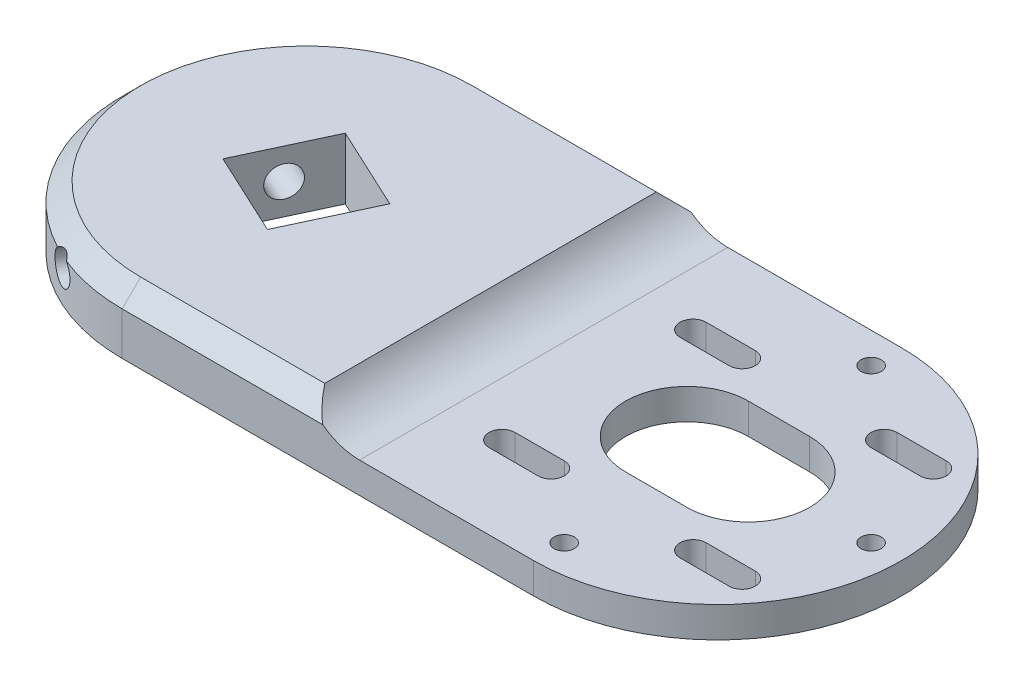
SolidWorks part; units mm, degrees
material "6063-O"
ref_plane "Front Plane" through (0, 0, 0) normal (0, 0, 1) x (1, 0, 0)
ref_plane "Top Plane" through (0, 0, 0) normal (0, 1, 0) x (1, 0, 0)
ref_plane "Right Plane" through (0, 0, 0) normal (1, 0, 0) x (0, 0, -1)
sketch "Sketch1" plane through (0, 0, 0) normal (0, 1, 0) x (1, 0, 0)
  line L0 (-33.5, 0) -> (33.5, 0) construction
  line L1 (-33.5, 30) -> (33.5, 30)
  line L2 (-33.5, -30) -> (33.5, -30)
  line L3 (28.5, 0) -> (38.5, 0) construction
  line L4 (28.5, 10) -> (38.5, 10)
  line L5 (28.5, -10) -> (38.5, -10)
  arc A0 (-33.5, 30) -> (-33.5, -30) centre (-33.5, 0) ccw
  arc A1 (33.5, -30) -> (33.5, 30) centre (33.5, 0) ccw
  arc A2 (28.5, 10) -> (28.5, -10) centre (28.5, 0) ccw
  circle A3 centre (33.5, 0) radius 13.5 construction
  arc A4 (38.5, -10) -> (38.5, 10) centre (38.5, 0) ccw
  point P10 (33.5, 0)
  dimension "D2" = 60
  dimension "D3" = 60
  dimension "D4" = 10
  dimension "D5" = 27
  dimension "D6" = 10
  dimension "D1" = 67
extrude "Boss-Extrude1" add sketch "Sketch1" along normal blind 5
sketch "Sketch2" plane through (0, 5, 0) normal (0, 1, 0) x (1, 0, 0)
  line L0 (13.9437, 15.5563) -> (21.9437, 15.5563) construction
  line L1 (13.9437, 17.6863) -> (21.9437, 17.6863)
  line L2 (13.9437, 13.4263) -> (21.9437, 13.4263)
  line L3 (33.5, 0) -> (33.5, 22) construction
  line L4 (17.9437, 15.5563) -> (33.5, 0) construction
  line L5 (11.5, 0) -> (55.5, 0) construction
  line L6 (53.0563, 15.5563) -> (45.0563, 15.5563) construction
  line L7 (53.0563, 17.6863) -> (45.0563, 17.6863)
  line L8 (53.0563, 13.4263) -> (45.0563, 13.4263)
  line L9 (53.0563, -15.5563) -> (45.0563, -15.5563) construction
  line L10 (53.0563, -17.6863) -> (45.0563, -17.6863)
  line L11 (53.0563, -13.4263) -> (45.0563, -13.4263)
  line L12 (13.9437, -15.5563) -> (21.9437, -15.5563) construction
  line L13 (13.9437, -17.6863) -> (21.9437, -17.6863)
  line L14 (13.9437, -13.4263) -> (21.9437, -13.4263)
  circle A0 centre (33.5, 0) radius 22 construction
  arc A1 (13.9437, 17.6863) -> (13.9437, 13.4263) centre (13.9437, 15.5563) ccw
  arc A2 (21.9437, 13.4263) -> (21.9437, 17.6863) centre (21.9437, 15.5563) ccw
  arc A3 (53.0563, 17.6863) -> (53.0563, 13.4263) centre (53.0563, 15.5563) cw
  arc A4 (45.0563, 13.4263) -> (45.0563, 17.6863) centre (45.0563, 15.5563) cw
  arc A5 (53.0563, -17.6863) -> (53.0563, -13.4263) centre (53.0563, -15.5563) ccw
  arc A6 (45.0563, -13.4263) -> (45.0563, -17.6863) centre (45.0563, -15.5563) ccw
  arc A7 (13.9437, -17.6863) -> (13.9437, -13.4263) centre (13.9437, -15.5563) cw
  arc A8 (21.9437, -13.4263) -> (21.9437, -17.6863) centre (21.9437, -15.5563) cw
  arc A9 (33.5, -30) -> (33.5, 30) centre (33.5, 0) ccw construction
  point P5 (17.9437, 15.5563)
  point P16 (49.0563, 15.5563)
  point P23 (49.0563, -15.5563)
  point P30 (17.9437, -15.5563)
  dimension "D1" = 44
  dimension "D3" = 2.13
  dimension "D2" = 8
  dimension "D4" = 45
extrude "Cut-Extrude1" cut sketch "Sketch2" against normal through all
sketch "Sketch8" plane through (0, 5, 0) normal (0, 1, 0) x (1, 0, 0)
  line L0 (-3.5, 30) -> (-3.5, -30)
  line L1 (33.5, 30) -> (-33.5, 30) construction
  line L2 (-33.5, -30) -> (33.5, -30) construction
  line L3 (-3.5, 30) -> (-33.5, 30)
  line L4 (-3.5, -30) -> (-33.5, -30)
  circle A0 centre (-33.5, 0) radius 30
  arc A1 (-33.5, 30) -> (-33.5, -30) centre (-33.5, 0) ccw construction
  line M6 (33.5, 30) -> (-33.5, 30)
  arc M7 (-33.5, 30) -> (-33.5, -30) centre (-33.5, 0) ccw
  line M8 (-33.5, -30) -> (33.5, -30)
  dimension "D1" = 60
extrude "Boss-Extrude2" add sketch "Sketch8" along normal blind 5 contours A0 M7 | A0 L0 M6 | A0 L0 M8 region at (-10.201, 5, -23.299) region at (-33.5, 5, 0) region at (-10.201, 5, 23.299)
fillet "Fillet1" radius 10 1 edges
sketch "Sketch9" plane through (0, 10, 0) normal (0, 1, 0) x (1, 0, 0)
  line L0 (-3.5, 0) -> (-63.5, 0) construction
  line L1 (-3.5, 30) -> (-3.5, -30) construction
  line L3 (-37.1277, 9.9669) -> (-23.5331, 3.6277)
  line L4 (-23.5331, 3.6277) -> (-29.8723, -9.9669)
  line L5 (-29.8723, -9.9669) -> (-43.4669, -3.6277)
  line L6 (-43.4669, -3.6277) -> (-37.1277, 9.9669)
  line L7 (-23.5331, 3.6277) -> (-43.4669, -3.6277) construction
  line L9 (-37.1277, 9.9669) -> (-29.8723, -9.9669) construction
  arc A0 (-33.5, 30) -> (-33.5, -30) centre (-33.5, 0) ccw construction
  point P15 (-33.5, 0)
  dimension "D5" = 30
  dimension "D1" = 65
  dimension "D3" = 15
extrude "Cut-Extrude2" cut sketch "Sketch9" against normal through all contours L6 L5 L4 L3 region at (-33.5, 10, 0)
hole_wizard "M4 Tapped Hole1" positions "Sketch12" profile "Sketch11" tap size "M4" standard "DIN" end condition through all
sketch "Sketch12" plane through (0, 5, 0) normal (0, 1, 0) x (1, 0, 0)
  line L0 (33.5, 25) -> (33.5, -25) construction
  line L3 (58.5, 0) -> (8.5, 0) construction
  circle A0 centre (33.5, 0) radius 25 construction
  arc A2 (33.5, -30) -> (33.5, 30) centre (33.5, 0) ccw construction
  point P6 (33.5, 25)
  point P7 (33.5, -25)
  point P11 (58.5, 0)
  dimension "D1" = 50
sketch "Sketch11" plane through (33.5, 5, -25) normal (1, 0, 0) x (0, 0, 1)
  line L0 (0, 0) -> (0, 5)
  line L1 (0, 5) -> (1.65, 5)
  line L2 (1.65, 5) -> (1.65, 0)
  line L5 (1.65, 0) -> (0, 0)
  line L11 (0, -6.35) -> (0, 107.95) construction
  dimension "Thru Tap Drill Dia." = 3.3
  dimension "Thru Tap Drill Depth" = 5
cosmetic thread "Hole Thread10" parameters "D1"=3, "D2"=4
cosmetic thread "Hole Thread11" parameters "D1"=3, "D2"=4
cosmetic thread "Hole Thread12" parameters "D1"=3, "D2"=4
hole_wizard "M6 Tapped Hole1" positions "3DSketch1" profile "Sketch13" tap size "M6" standard "DIN" end condition through all
sketch3d "3DSketch1"
  line L0 (-37.1277, 10, -9.9669) -> (-43.4669, 0, 3.6277) construction
  line L3 (-37.1277, 0, -9.9669) -> (-43.4669, 10, 3.6277) construction
  point P0 (-40.2973, 5, -3.1696)
sketch "Sketch13" plane through (-40.2973, 5, -3.1696) normal (0, 1, 0) x (0.4226, 0, -0.9063)
  line L0 (0, 0) -> (0, 32.3678)
  line L1 (0, 32.3678) -> (2.5, 32.3678)
  line L2 (2.5, 32.3678) -> (2.5, 0)
  line L5 (2.5, 0) -> (0, 0)
  line L11 (0, -6.35) -> (0, 107.95) construction
  dimension "Thru Tap Drill Dia." = 5
  dimension "Thru Tap Drill Depth" = 32.3678
cosmetic thread "Hole Thread6" parameters "D2"=6
hole_wizard "M6 Tapped Hole2" positions "3DSketch2" profile "Sketch14" tap size "M6" standard "DIN" end condition through all
sketch3d "3DSketch2"
  line L0 (-43.4669, 0, 3.6277) -> (-29.8723, 10, 9.9669) construction
  line L3 (-43.4669, 10, 3.6277) -> (-29.8723, 0, 9.9669) construction
  point P0 (-36.6696, 5, 6.7973)
sketch "Sketch14" plane through (-36.6696, 5, 6.7973) normal (0, 1, 0) x (-0.9063, 0, -0.4226)
  line L0 (0, 0) -> (0, 32.3678)
  line L1 (0, 32.3678) -> (2.5, 32.3678)
  line L2 (2.5, 32.3678) -> (2.5, 0)
  line L5 (2.5, 0) -> (0, 0)
  line L11 (0, -6.35) -> (0, 107.95) construction
  dimension "Thru Tap Drill Dia." = 5
  dimension "Thru Tap Drill Depth" = 32.3678
cosmetic thread "Hole Thread5" parameters "D2"=6
chamfer "Chamfer1" distance 3 angle 45 3 edges at (-18.5, 10, -30) (-18.5, 10, 30) (-63.5, 10, 0)
